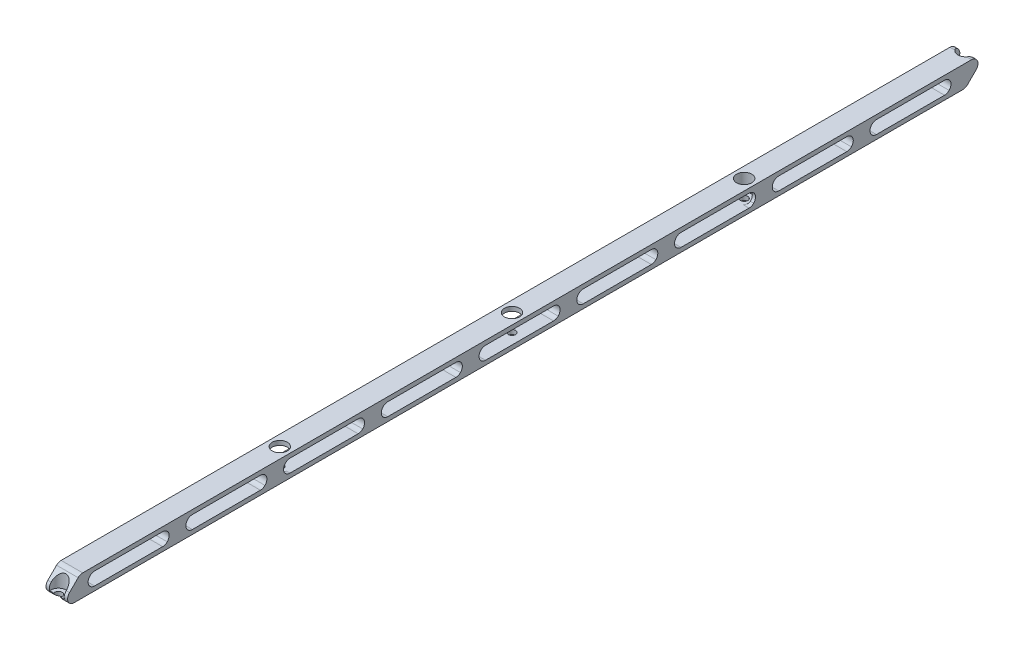
SolidWorks part; units mm, degrees
material "ABS"
ref_plane "Front Plane" through (0, 0, 0) normal (0, 0, 1) x (1, 0, 0)
ref_plane "Top Plane" through (0, 0, 0) normal (0, 1, 0) x (1, 0, 0)
ref_plane "Right Plane" through (0, 0, 0) normal (1, 0, 0) x (0, 0, -1)
sketch "Sketch1" plane through (0, 0, 0) normal (1, 0, 0) x (0, 0, -1)
  line L0 (0, 5) -> (0, -5) construction
  line L1 (-215, 5) -> (215, 5)
  line L2 (-215, 5) -> (-215, -5)
  line L3 (-215, -5) -> (215, -5)
  line L4 (215, 5) -> (215, -5)
  line L5 (-215, 5) -> (215, -5) construction
  line L6 (-215, -5) -> (215, 5) construction
  line L7 (-205.5, -3) -> (-199.5, 3)
  line L8 (-199.5, 3) -> (-159.5, 3)
  line L9 (-159.5, 3) -> (-165.5, -3)
  line L10 (-165.5, -3) -> (-205.5, -3)
  line L11 (-215, -5) -> (-205, 5)
  line L12 (-154.25, 3) -> (-114.25, 3)
  line L13 (-120.25, -3) -> (-160.25, -3)
  line L14 (-114.25, 3) -> (-120.25, -3)
  line L15 (-160.25, -3) -> (-154.25, 3)
  line L16 (-109, 3) -> (-69, 3)
  line L17 (-75, -3) -> (-115, -3)
  line L18 (-69, 3) -> (-75, -3)
  line L19 (-115, -3) -> (-109, 3)
  line L20 (-63.75, 3) -> (-23.75, 3)
  line L21 (-29.75, -3) -> (-69.75, -3)
  line L22 (-23.75, 3) -> (-29.75, -3)
  line L23 (-69.75, -3) -> (-63.75, 3)
  line L24 (-18.5, 3) -> (21.5, 3)
  line L25 (15.5, -3) -> (-24.5, -3)
  line L26 (21.5, 3) -> (15.5, -3)
  line L27 (-24.5, -3) -> (-18.5, 3)
  line L28 (26.75, 3) -> (66.75, 3)
  line L29 (60.75, -3) -> (20.75, -3)
  line L30 (66.75, 3) -> (60.75, -3)
  line L31 (20.75, -3) -> (26.75, 3)
  line L32 (72, 3) -> (112, 3)
  line L33 (106, -3) -> (66, -3)
  line L34 (112, 3) -> (106, -3)
  line L35 (66, -3) -> (72, 3)
  line L36 (117.25, 3) -> (157.25, 3)
  line L37 (151.25, -3) -> (111.25, -3)
  line L38 (157.25, 3) -> (151.25, -3)
  line L39 (111.25, -3) -> (117.25, 3)
  line L40 (162.5, 3) -> (202.5, 3)
  line L41 (196.5, -3) -> (156.5, -3)
  line L42 (202.5, 3) -> (196.5, -3)
  line L43 (156.5, -3) -> (162.5, 3)
  line L44 (215, 5) -> (205, -5)
  point P0 (0, 0)
  dimension "D1" = 10
  dimension "D2" = 430
  dimension "D3" = 2
  dimension "D4" = 2
  dimension "D5" = 45
  dimension "D6" = 40
  dimension "D7" = 45
  dimension "D8" = 5.5
  dimension "D10" = 45
  dimension "D11" = 5.25
  dimension "D9" = 9
extrude "Boss-Extrude1" add sketch "Sketch1" along normal blind 10 contours L44 L1 L11 L3 L37 L39 L36 L38 L29 L31 L28 L30 L21 L23 L20 L22 L13 L15 L12 L14 L9 L10 L7 L8 L17 L19 L16 L18 L25 L27 L24 L26 L33 L35 L32 L34 L41 L43 L40 L42 region at (0, 4.5699, -5)
fillet "Fillet1" radius 3 40 edges at (5, -5, 215) (5, 5, 205) (5, -5, -205) (5, 5, -215) (5, -3, -156.5) (5, -3, -151.25) (5, 3, -162.5) (5, 3, -157.25) (5, -3, -106) (5, -3, -111.25) (5, 3, -112) (5, 3, -117.25) (5, -3, -66) (5, -3, -60.75) (5, 3, -72) (5, 3, -66.75) (5, -3, -15.5) (5, -3, -20.75) (5, 3, -21.5) (5, 3, -26.75) (5, -3, 24.5) (5, -3, 29.75) (5, 3, 18.5) (5, 3, 23.75) (5, -3, 75) (5, -3, 69.75) (5, 3, 69) (5, 3, 63.75) (5, -3, 115) (5, -3, 120.25) (5, 3, 109) (5, 3, 114.25) (5, -3, 160.25) (5, 3, 159.5) (5, 3, 154.25) (5, -3, 205.5) (5, 3, 199.5) (5, -3, -196.5) (5, 3, -202.5) (5, -3, 165.5)
hole_wizard "CBORE for M3 Hex Head Cap Screw1" positions "Sketch3" profile "Sketch2" counterbore size "M3" standard "ISO" end condition through all
sketch "Sketch3" plane through (0, 5, 0) normal (0, 1, 0) x (1, 0, 0)
  line L0 (10, -203.7574) -> (10, 207.7574) construction
  line L1 (10, -215) -> (0, -215) construction
  point P0 (5, -210)
  point P2 (5, 0)
  point P4 (5, -107.5)
  point P6 (5, 107.5)
  point P8 (5, 210)
  dimension "D1" = 5
  dimension "D2" = 102.5
  dimension "D3" = 107.5
  dimension "D4" = 107.5
  dimension "D5" = 102.5
  dimension "D6" = 5
sketch "Sketch2" plane through (5, 5, 210) normal (1, 0, 0) x (0, 0, 1)
  line L0 (0, 0) -> (0, 10)
  line L1 (0, 10) -> (1.7, 10)
  line L3 (1.7, 10) -> (1.7, 8)
  line L4 (1.7, 8) -> (3.5, 8)
  line L5 (3.5, 8) -> (3.5, 0)
  line L7 (3.5, 0) -> (0, 0)
  line L11 (0, -6.35) -> (0, 107.95) construction
  dimension "Thru Hole Dia." = 3.4
  dimension "Thru Hole Depth" = 10
  dimension "C'Bore Dia." = 7
  dimension "C'Bore Depth" = 8
